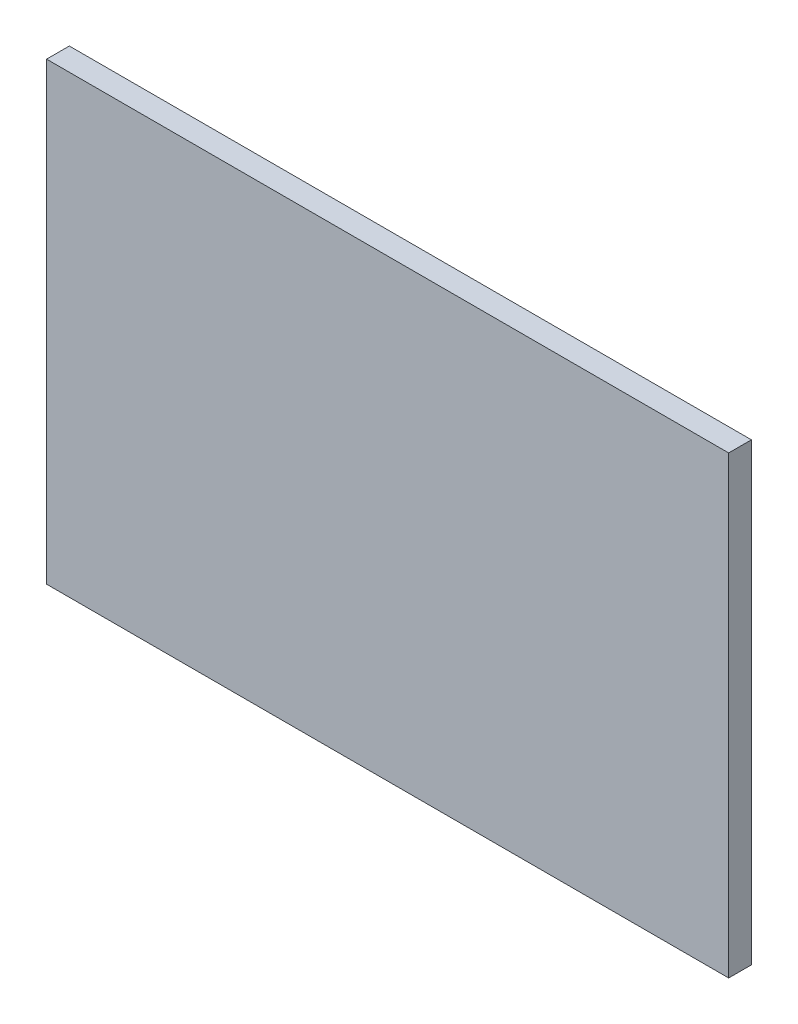
SolidWorks part; units mm, degrees
ref_plane "Ebene vorne" through (0, 0, 0) normal (0, 0, 1) x (1, 0, 0)
ref_plane "Ebene oben" through (0, 0, 0) normal (0, 1, 0) x (1, 0, 0)
ref_plane "Ebene rechts" through (0, 0, 0) normal (1, 0, 0) x (0, 0, -1)
other "Massenmittelpunkt"
sketch "Skizze1" plane through (0, 0, 0) normal (0, 0, 1) x (1, 0, 0)
  line L0 (-15, 10) -> (-15, -10)
  line L1 (-15, -10) -> (15, -10)
  line L2 (15, -10) -> (15, 10)
  line L3 (15, 10) -> (-15, 10)
  line L4 (-15, 0) -> (15, 0) construction
  line L5 (0, 10) -> (0, -10) construction
  point P3 (0, 10)
  point P5 (15, 0)
  point P6 (0, -10)
  point P7 (-15, 0)
  point P12 (0, 0)
  dimension "D1" = 30
  dimension "D2" = 30
  dimension "D3" = 20
  dimension "D4" = 20
  dimension "D5" = 90
ref_axis "Achse1" through (11, 0, 0) along (-1, 0, 0)
ref_plane "Rotation_Plane" through (0, 0, 0) normal (0, 0, -1) x (-1, 0, 0)
ref_plane "Top_Plane" through (0, 0, 1) normal (0, 0, -1) x (-1, 0, 0)
sketch "Skizze2" plane through (0, 0, 1) normal (0, 0, -1) x (-1, 0, 0)
  line L0 (15, 10) -> (15, -10)
  line L1 (15, -10) -> (-15, -10)
  line L2 (-15, -10) -> (-15, 10)
  line L3 (-15, 10) -> (15, 10)
  line L4 (0, 10) -> (0, -10) construction
  line L5 (15, 0) -> (-15, 0) construction
  line L6 (0, 10) -> (0, -10) construction
  line L7 (0, 10) -> (0, -10) construction
  point P0 (0, 0)
  point P6 (0, 10)
  point P7 (-15, 0)
  point P8 (0, -10)
  point P9 (15, 0)
  point P14 (0, 0)
  dimension "D5" = 90
  dimension "D1" = 20
  dimension "D2" = 20
  dimension "D3" = 30
  dimension "D4" = 30
  dimension "D6" = 0
loft "Ausformung2" add profiles "Skizze1", "Skizze2" connector at (-15, -10, 0) connector at (-15, -10, 1)
ref_point "SWASI_Vision_Point_1_T"
ref_point "SWASI_Vision_Point_1_B"
ref_point "SWASI_Vision_Point_2_T"
ref_point "SWASI_Vision_Point_2_B"
ref_point "SWASI_Vision_Point_3_T"
ref_point "SWASI_Vision_Point_3_B"
ref_point "SWASI_Vision_Point_4_T"
ref_point "SWASI_Vision_Point_4_B"
sketch "Skizze3" plane through (0, 0, 1) normal (0, 0, 1) x (1, 0, 0)
  line L0 (-15, 0) -> (15, 0) construction
  line L1 (0, 10) -> (0, -10) construction
  line L3 (-14, -9) -> (14, -9)
  line L4 (15, 10) -> (-15, 10)
  line L5 (-15, 10) -> (-15, -10)
  line L6 (-15, -10) -> (15, -10)
  line L7 (15, -10) -> (15, 10)
  line L8 (15, 10) -> (-15, 10) construction
  line L9 (-15, 10) -> (-15, -10) construction
  line L10 (-15, -10) -> (15, -10) construction
  line L11 (15, -10) -> (15, 10) construction
  line L12 (-14, -9) -> (-14, 9)
  line L13 (-14, 9) -> (14, 9)
  line L14 (14, -9) -> (14, 9)
  line L15 (-14, -9) -> (14, 9) construction
  line L16 (-14, 9) -> (14, -9) construction
  point P8 (0, 0)
  point P9 (0, 0)
  dimension "D2" = 28
  dimension "D3" = 18
  dimension "D1" = 0
ref_point "SWASI_Laser_1_T"
ref_point "SWASI_Laser_2_T"
ref_point "SWASI_Laser_3_T"
ref_point "SWASI_Laser_4_T"
ref_point "SWASI_Gripping_Point"
sketch "Skizze4" plane through (0, 0, 0) normal (0, 0, -1) x (-1, 0, 0)
  line L1 (14, 9) -> (-14, 9)
  line L2 (14, 9) -> (14, -9)
  line L3 (14, -9) -> (-14, -9)
  line L4 (-14, 9) -> (-14, -9)
  line L5 (14, 9) -> (-14, -9) construction
  line L6 (14, -9) -> (-14, 9) construction
  point P0 (0, 0)
  point P2 (0, 0)
  dimension "D1" = 28
  dimension "D2" = 18
ref_point "SWASI_Laser_1_B"
ref_point "SWASI_Laser_2_B"
ref_point "SWASI_Laser_3_B"
ref_point "SWASI_Laser_4_B"
ref_plane "SWASI_Top_Plane" through (0, 0, 1) normal (0, 0, -1) x (-1, 0, 0)
ref_plane "SWASI_Bottom_Plane" through (0, 0, 0) normal (0, 0, -1) x (-1, 0, 0)
ref_axis "SWASI_Bottom_Axis" through (15, -10, 0) along (-1, 0, 0)
ref_axis "SWASI_Top_Axis" through (15, -10, 1) along (-1, 0, 0)
sketch "Skizze5" plane through (0, 0, 0) normal (0, 0, -1) x (-1, 0, 0)
  line L0 (15, -10) -> (-15, -10) construction
  line L1 (15, -10) -> (-15, -10)
  point P2 (0, -10)
sketch "Skizze6" plane through (0, 0, 1) normal (0, 0, 1) x (1, 0, 0)
  line L0 (15, -10) -> (-15, -10) construction
  point P0 (0, -10)
  point P1 (-12.736, 25.2765)
ref_point "SWASI_Axis_Center_B"
ref_point "SWASI_Axis_Center_T"
ref_plane "SWASI_Axis_T_Plane" through (0, -10, 1) normal (-1, 0, 0) x (0, 0, 1)
ref_plane "SWASI_Axis_B_Plane" through (0, -10, 0) normal (-1, 0, 0) x (0, 0, 1)
ref_plane "Bottom_Reference" through (0, 0, 3) normal (0, 0, -1) x (-1, 0, 0)
ref_plane "Top_Reference" through (0, 0, -2) normal (0, 0, 1) x (1, 0, 0)
sketch "Skizze7" plane through (0, 229.1773, 3) normal (0, 0, -1) x (1, 0, 0)
  point P0 (-15, 239.1773)
ref_point "SWASI_Front_Bottom_Reference"
ref_plane "SWASI_Front_Plane_B" through (0, -10, 0) normal (0, 1, 0) x (1, 0, 0.0001)
sketch "Skizze9" plane through (0, 229.1773, -2) normal (0, 0, 1) x (-1, 0, 0)
  point P0 (-15, 239.1773)
ref_point "SWASI_Front_Top_Reference"
ref_plane "SWASI_Front_Plane_T" through (0, -10, 0) normal (0, -1, 0) x (-1, 0, -0.0003)
sketch "Skizze10" plane through (0, 0, 0) normal (0, 0, -1) x (-1, 0, 0)
  line L0 (-17, 12) -> (-17, -8) construction
  line L1 (-17, 12) -> (3, 12) construction
  point P2 (-15, -10)
  point P4 (15, 10)
  dimension "D1" = 20
  dimension "D2" = 20
  dimension "D3" = 2
  dimension "D4" = 2
ref_point "Punkt44"
equation "\"Length_1\" = 20"
equation "\"Length_2\" = 20mm"
equation "\"Length_3\" = 30"
equation "\"Length_4\" = 30"
equation "\"D1@Skizze1\"=\"Length_3\""
equation "\"D2@Skizze1\"=\"Length_4\""
equation "\"D3@Skizze1\"=\"Length_1\""
equation "\"D4@Skizze1\"=\"Length_2\""
equation "\"Angle_1\"= 90"
equation "\"Angle_2\"= 90"
equation "\"Plane_Angle\" = 0"
equation "\"D5@Skizze1\"=\"Angle_1\""
equation "\"Plane_Distance\" = 0"
equation "\"Length_1_1\" = 20"
equation "\"Length_1_2\" = 20"
equation "\"Length_1_3\" = 30"
equation "\"Length_1_4\"= 30"
equation "\"Angle_3\"= 90"
equation "\"Angle_4\"= 90"
equation "\"D1@Skizze2\"=\"Length_1_1\""
equation "\"D2@Skizze2\"=\"Length_1_2\""
equation "\"D3@Skizze2\"=\"Length_1_3\""
equation "\"D4@Skizze2\"=\"Length_1_4\""
equation "\"D5@Skizze2\"=\"Angle_3\""
equation "\"Angle_Plane_rot\"= 0"
equation "\"D6@Skizze2\"=\"Angle_Plane_rot\""
